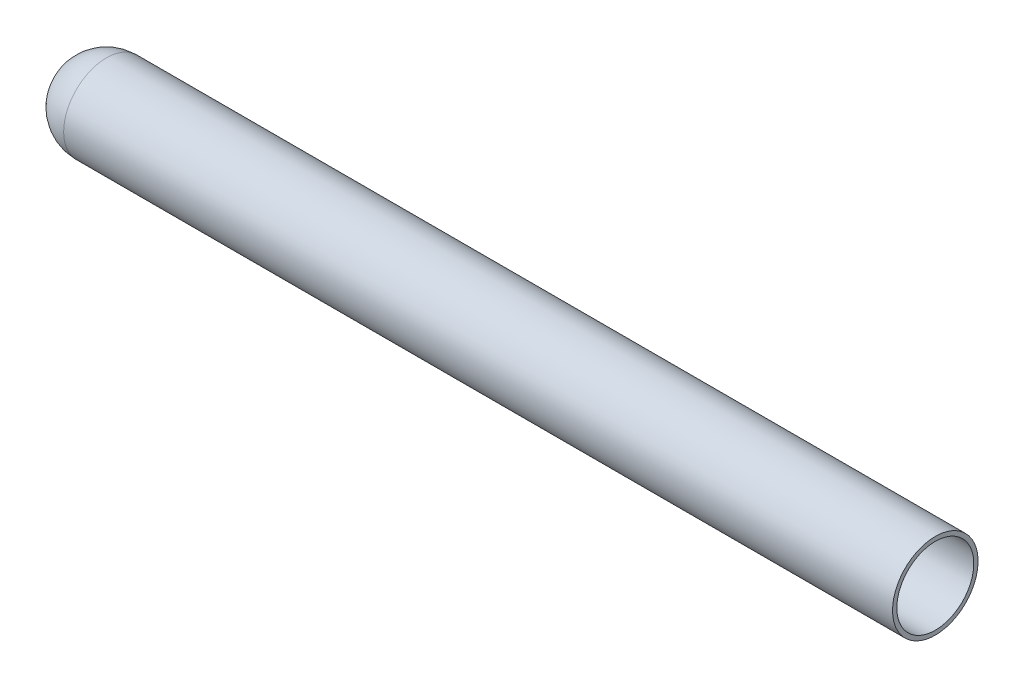
SolidWorks part; units mm, degrees
ref_plane "Front Plane" through (0, 0, 0) normal (0, 0, 1) x (1, 0, 0)
ref_plane "Top Plane" through (0, 0, 0) normal (0, 1, 0) x (1, 0, 0)
ref_plane "Right Plane" through (0, 0, 0) normal (1, 0, 0) x (0, 0, -1)
sketch "rootSketch" plane through (0, 0, 0) normal (0, 1, 0) x (1, 0, 0)
  line L0 (0, 0) -> (12000, 0) construction
  line L1 (31.75, -31.75) -> (31.75, 31.75) construction
  line L2 (0, 0) -> (647, 0) construction
  line L3 (31.75, -31.75) -> (647, -31.75)
  line L4 (647, -31.75) -> (647, 0) construction
  line L5 (647, -31.75) -> (647, -28.575)
  line L6 (647, -28.575) -> (31.75, -28.575)
  line L7 (3.175, 0) -> (0, 0)
  arc A1 (31.75, -31.75) -> (0, 0) centre (31.75, 0) cw
  arc A2 (31.75, -28.575) -> (3.175, 0) centre (31.75, 0) cw
  point P5 (31.75, 0)
  dimension "rootMaxThickness" = 63.5
  dimension "D1" = 647
  dimension "D2" = 3.175
revolve "Revolve1" add sketch "rootSketch" angle 360 about L0
ref_plane "Plane1" through (5330, 0, 0) normal (1, 0, 0) x (0, 0, -1)
equation "\"length\"= 0.647"
equation "\"D1@rootSketch\" = \"length\""
equation "\"diameter\"= 0.0635"
equation "\"rootMaxThickness@rootSketch\"=\"diameter\""
